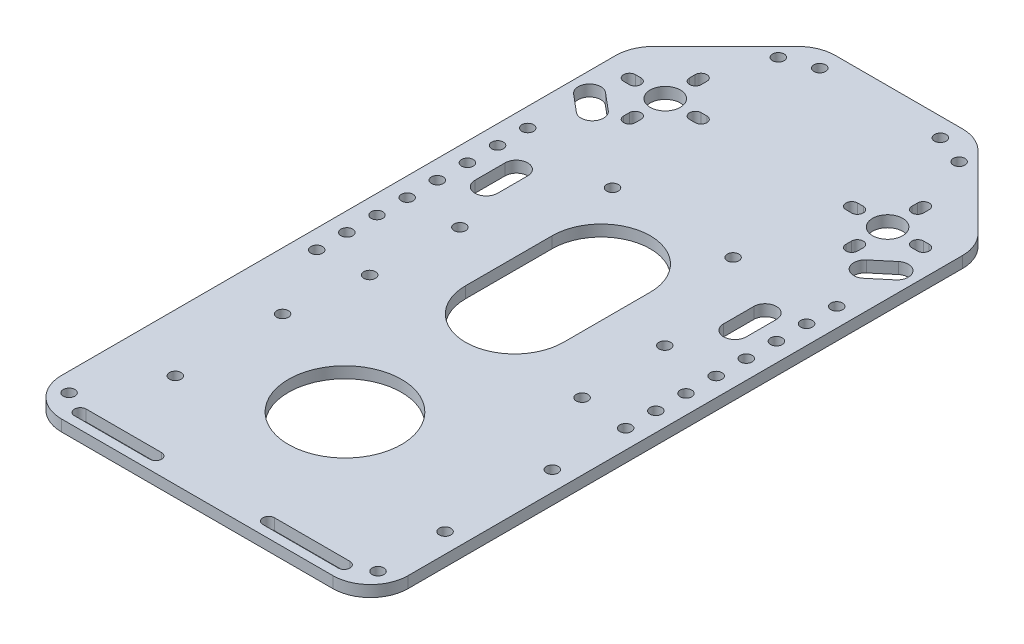
SolidWorks part; units mm, degrees
material "Thornel Mat VMA"
ref_plane "Front Plane" through (0, 0, 0) normal (0, 0, 1) x (1, 0, 0)
ref_plane "Top Plane" through (0, 0, 0) normal (0, 1, 0) x (1, 0, 0)
ref_plane "Right Plane" through (0, 0, 0) normal (1, 0, 0) x (0, 0, -1)
sketch "Sketch1" plane through (0, 0, 0) normal (0, 1, 0) x (1, 0, 0)
  line L0 (0, 0) -> (0, -275.7813) construction
  line L1 (0, 0) -> (121.6069, 0) construction
  line L2 (37.5, 0) -> (39, 0) construction
  line L3 (37.5, 1.55) -> (39, 1.55)
  line L4 (37.5, -1.55) -> (39, -1.55)
  line L5 (29.5, -8) -> (29.5, -9.5) construction
  line L6 (31.05, -8) -> (31.05, -9.5)
  line L7 (27.95, -8) -> (27.95, -9.5)
  line L8 (21.5, 0) -> (20, 0) construction
  line L9 (21.5, -1.55) -> (20, -1.55)
  line L10 (21.5, 1.55) -> (20, 1.55)
  line L11 (29.5, 8) -> (29.5, 9.5) construction
  line L12 (27.95, 8) -> (27.95, 9.5)
  line L13 (31.05, 8) -> (31.05, 9.5)
  line L14 (41, -25) -> (41, -67.0317) construction
  line L15 (-46, 32.5) -> (46, 32.5)
  line L16 (46, 32.5) -> (46, -153.73)
  line L17 (46, -153.73) -> (-46, -153.73)
  line L18 (-46, 32.5) -> (-46, -153.73)
  line L19 (-29.5, 8) -> (-29.5, 9.5) construction
  line L20 (-27.95, 8) -> (-27.95, 9.5)
  line L21 (-31.05, 8) -> (-31.05, 9.5)
  line L22 (-21.5, 0) -> (-20, 0) construction
  line L23 (-21.5, -1.55) -> (-20, -1.55)
  line L24 (-21.5, 1.55) -> (-20, 1.55)
  line L25 (-29.5, -8) -> (-29.5, -9.5) construction
  line L26 (-31.05, -8) -> (-31.05, -9.5)
  line L27 (-27.95, -8) -> (-27.95, -9.5)
  line L28 (-37.5, 0) -> (-39, 0) construction
  line L29 (-37.5, 1.55) -> (-39, 1.55)
  line L30 (-37.5, -1.55) -> (-39, -1.55)
  line L31 (0, -46.5) -> (0, -69.5) construction
  line L32 (13, -46.5) -> (13, -69.5)
  line L33 (-13, -46.5) -> (-13, -69.5)
  line L34 (0, -69.5) -> (-54.3785, -44.1429) construction
  line L35 (0, -69.5) -> (-45.0064, -85.881) construction
  line L36 (12.327, -114.5) -> (110.2373, -114.5) construction
  line L37 (5, -92.7422) -> (5, -214.7614) construction
  line L38 (29.5, 0) -> (50.8627, -25.4591) construction
  line L41 (40.7972, -8.7963) -> (36.2009, -12.653) construction
  line L42 (42.7255, -11.0944) -> (38.1293, -14.9511)
  line L43 (38.8688, -6.4981) -> (34.2725, -10.3549)
  line L44 (-40.7972, -8.7963) -> (-36.2009, -12.653) construction
  line L45 (-42.7255, -11.0944) -> (-38.1293, -14.9511)
  line L46 (-38.8688, -6.4981) -> (-34.2725, -10.3549)
  line L47 (33, -36) -> (33, -44) construction
  line L48 (36, -36) -> (36, -44)
  line L49 (30, -36) -> (30, -44)
  line L50 (-33, -36) -> (-33, -44) construction
  line L51 (-36, -36) -> (-36, -44)
  line L52 (-30, -36) -> (-30, -44)
  line L53 (15, -149.73) -> (35, -149.73) construction
  line L54 (15, -148.18) -> (35, -148.18)
  line L55 (15, -151.28) -> (35, -151.28)
  line L56 (-15, -149.73) -> (-35, -149.73) construction
  line L57 (-15, -148.18) -> (-35, -148.18)
  line L58 (-15, -151.28) -> (-35, -151.28)
  circle A0 centre (29.5, 0) radius 4
  arc A1 (37.5, 1.55) -> (37.5, -1.55) centre (37.5, 0) ccw
  arc A2 (39, -1.55) -> (39, 1.55) centre (39, 0) ccw
  arc A3 (31.05, -8) -> (27.95, -8) centre (29.5, -8) ccw
  arc A4 (27.95, -9.5) -> (31.05, -9.5) centre (29.5, -9.5) ccw
  arc A5 (21.5, -1.55) -> (21.5, 1.55) centre (21.5, 0) ccw
  arc A6 (20, 1.55) -> (20, -1.55) centre (20, 0) ccw
  arc A7 (27.95, 8) -> (31.05, 8) centre (29.5, 8) ccw
  arc A8 (31.05, 9.5) -> (27.95, 9.5) centre (29.5, 9.5) ccw
  circle A9 centre (41, -25) radius 1.55
  circle A13 centre (-29.5, 0) radius 4
  arc A14 (-27.95, 8) -> (-31.05, 8) centre (-29.5, 8) cw
  arc A15 (-31.05, 9.5) -> (-27.95, 9.5) centre (-29.5, 9.5) cw
  arc A16 (-21.5, -1.55) -> (-21.5, 1.55) centre (-21.5, 0) cw
  arc A17 (-20, 1.55) -> (-20, -1.55) centre (-20, 0) cw
  arc A18 (-31.05, -8) -> (-27.95, -8) centre (-29.5, -8) cw
  arc A19 (-27.95, -9.5) -> (-31.05, -9.5) centre (-29.5, -9.5) cw
  arc A20 (-37.5, 1.55) -> (-37.5, -1.55) centre (-37.5, 0) cw
  arc A21 (-39, -1.55) -> (-39, 1.55) centre (-39, 0) cw
  circle A22 centre (16, 27.5) radius 1.55
  circle A23 centre (16, -27.5) radius 1.55
  circle A24 centre (-16, -27.5) radius 1.55
  circle A25 centre (-16, 27.5) radius 1.55
  circle A26 centre (-27.1892, -56.8215) radius 1.55
  circle A27 centre (-28.1908, -79.7606) radius 1.55
  circle A28 centre (28.1908, -79.7606) radius 1.55
  circle A29 centre (27.1892, -56.8215) radius 1.55
  arc A30 (13, -46.5) -> (-13, -46.5) centre (0, -46.5) ccw
  arc A31 (-13, -69.5) -> (13, -69.5) centre (0, -69.5) ccw
  circle A36 centre (40.79, -100.27) radius 1.55
  circle A37 centre (40.79, -128.73) radius 1.55
  circle A38 centre (-30.79, -128.73) radius 1.55
  circle A39 centre (-30.79, -100.27) radius 1.55
  circle A45 centre (41, -33) radius 1.55
  circle A46 centre (41, -41) radius 1.55
  circle A47 centre (41, -49) radius 1.55
  circle A48 centre (41, -57) radius 1.55
  circle A49 centre (41, -65) radius 1.55
  circle A50 centre (41, -73) radius 1.55
  circle A51 centre (41, -81) radius 1.55
  circle A52 centre (-41, -81) radius 1.55
  circle A53 centre (-41, -73) radius 1.55
  circle A54 centre (-41, -65) radius 1.55
  circle A55 centre (-41, -57) radius 1.55
  circle A56 centre (-41, -49) radius 1.55
  circle A57 centre (-41, -41) radius 1.55
  circle A58 centre (-41, -33) radius 1.55
  circle A59 centre (-41, -25) radius 1.55
  arc A60 (42.7255, -11.0944) -> (38.8688, -6.4981) centre (40.7972, -8.7963) ccw
  arc A61 (34.2725, -10.3549) -> (38.1293, -14.9511) centre (36.2009, -12.653) ccw
  arc A62 (-42.7255, -11.0944) -> (-38.8688, -6.4981) centre (-40.7972, -8.7963) cw
  arc A63 (-34.2725, -10.3549) -> (-38.1293, -14.9511) centre (-36.2009, -12.653) cw
  arc A64 (36, -36) -> (30, -36) centre (33, -36) ccw
  arc A65 (30, -44) -> (36, -44) centre (33, -44) ccw
  arc A66 (-36, -36) -> (-30, -36) centre (-33, -36) cw
  arc A67 (-30, -44) -> (-36, -44) centre (-33, -44) cw
  arc A68 (15, -148.18) -> (15, -151.28) centre (15, -149.73) ccw
  arc A69 (35, -151.28) -> (35, -148.18) centre (35, -149.73) ccw
  arc A70 (-15, -148.18) -> (-15, -151.28) centre (-15, -149.73) cw
  arc A71 (-35, -151.28) -> (-35, -148.18) centre (-35, -149.73) cw
  circle A72 centre (24, 24.5) radius 1.55
  circle A73 centre (-24, 24.5) radius 1.55
  circle A74 centre (41, -146.73) radius 1.55
  circle A75 centre (-41, -146.73) radius 1.55
  circle A76 centre (0, -114.5) radius 15
  point P8 (38.25, 0)
  point P18 (29.5, -8.75)
  point P25 (20.75, 0)
  point P32 (29.5, 8.75)
  point P37 (29.5, 0)
  point P50 (0, -153.73)
  point P51 (0, 32.5)
  point P55 (-29.5, 8.75)
  point P62 (-20.75, 0)
  point P69 (-29.5, -8.75)
  point P76 (-38.25, 0)
  point P98 (0, -58)
  point P145 (38.499, -10.7246)
  point P152 (-38.499, -10.7246)
  point P159 (33, -40)
  point P166 (-33, -40)
  point P173 (25, -149.73)
  point P180 (-25, -149.73)
  dimension "D1" = 8
  dimension "D2" = 1.55
  dimension "D4" = 8
  dimension "D5" = 4
  dimension "D6" = 3.1
  dimension "D7" = 25
  dimension "D8" = 41
  dimension "D9" = 59
  dimension "D10" = 3.1
  dimension "D11" = 16
  dimension "D12" = 27.5
  dimension "D13" = 13
  dimension "D15" = 30
  dimension "D18" = 46.5
  dimension "D19" = 5
  dimension "D20" = 8
  dimension "D21" = 45
  dimension "D25" = 14.23
  dimension "D26" = 35.79
  dimension "D27" = 3
  dimension "D30" = 25
  dimension "D33" = 3
  dimension "D36" = 1.55
  dimension "D40" = 8
  dimension "D41" = 3
  dimension "D42" = 5
  dimension "D43" = 7
  dimension "D44" = 30
  dimension "D3" = 1.5
  dimension "D14" = 23
  dimension "D16" = 30
  dimension "D17" = 70
  dimension "D22" = 45
  dimension "D23" = 50
  dimension "D24" = 5
  dimension "D28" = 14
  dimension "D29" = 6
  dimension "D31" = 5
  dimension "D32" = 8
  dimension "D34" = 8
  dimension "D35" = 40
  dimension "D37" = 20
  dimension "D38" = 4
  dimension "D39" = 25
extrude "Boss-Extrude1" add sketch "Sketch1" along normal blind 3
chamfer "Chamfer1" distance 25 angle 45 2 edges at (46, 1.5, -32.5) (-46, 1.5, -32.5)
fillet "Fillet1" radius 10 6 edges at (-46, 1.5, 153.73) (46, 1.5, 153.73) (46, 1.5, -7.5) (21, 1.5, -32.5) (-46, 1.5, -7.5) (-21, 1.5, -32.5)
